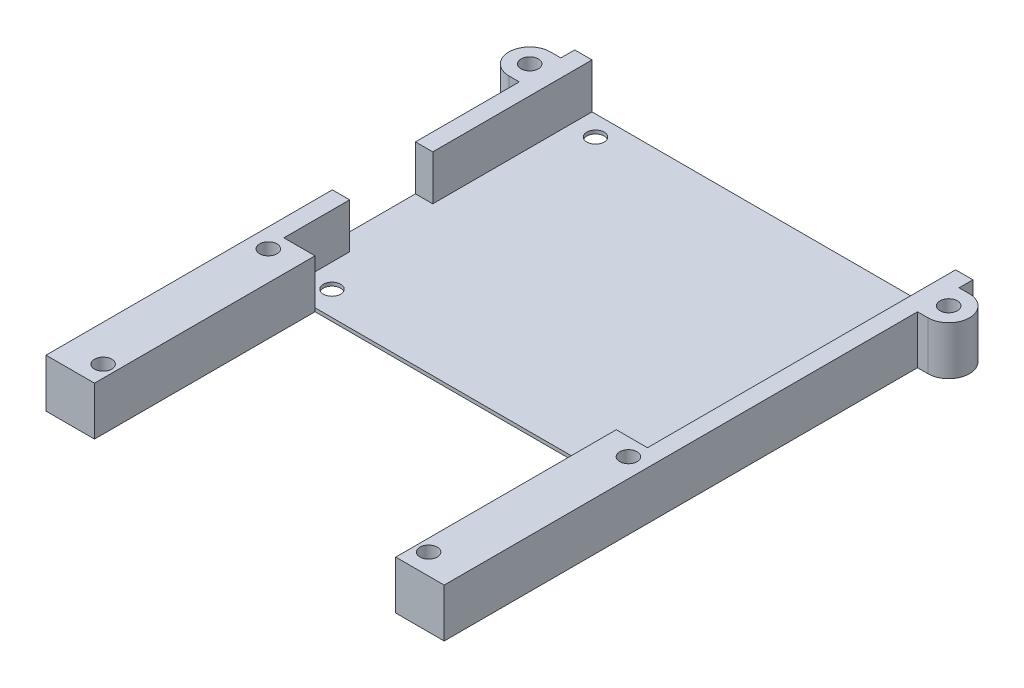
SolidWorks part; units mm, degrees
ref_plane "Front Plane" through (0, 0, 0) normal (0, 0, 1) x (1, 0, 0)
ref_plane "Top Plane" through (0, 0, 0) normal (0, 1, 0) x (1, 0, 0)
ref_plane "Right Plane" through (0, 0, 0) normal (1, 0, 0) x (0, 0, -1)
sketch "Sketch1" plane through (0, 0, 0) normal (0, 1, 0) x (1, 0, 0)
  line L0 (0, 0) -> (0, 76.35) construction
  line L1 (-28.75, 76.35) -> (28.75, 76.35)
  line L2 (28.75, 76.35) -> (28.75, 0)
  line L3 (28.75, 0) -> (21.75, 0)
  line L4 (21.75, 0) -> (21.75, 31.85)
  line L5 (21.75, 31.85) -> (-21.75, 31.85)
  line L6 (-21.75, 31.85) -> (-21.75, 0)
  line L7 (-21.75, 0) -> (-28.75, 0)
  line L8 (-28.75, 0) -> (-28.75, 76.35)
  line L9 (-26.25, 76.35) -> (-26.25, 31.85)
  line L14 (-26.25, 31.85) -> (-21.75, 31.85)
  line L15 (26.25, 76.35) -> (26.25, 31.85)
  line L16 (26.25, 31.85) -> (21.75, 31.85)
  line L17 (28.75, 74.35) -> (30.25, 74.35)
  line L18 (-28.75, 41.35) -> (-26.25, 41.35)
  line L19 (-28.75, 41.35) -> (-28.75, 53.35)
  line L20 (-28.75, 53.35) -> (-26.25, 53.35)
  line L21 (-26.25, 41.35) -> (-26.25, 53.35)
  line L22 (30.25, 68.35) -> (28.75, 68.35)
  line L23 (-30.25, 68.35) -> (-28.75, 68.35)
  line L24 (-28.75, 74.35) -> (-30.25, 74.35)
  arc A0 (30.25, 68.35) -> (30.25, 74.35) centre (30.25, 71.35) ccw
  arc A1 (-30.25, 68.35) -> (-30.25, 74.35) centre (-30.25, 71.35) cw
  point P10 (0, 76.35)
  point P16 (-27.5, 41.35)
  point P17 (-22.85, 73.45)
  point P18 (22.85, 73.45)
  point P23 (22.85, 35.4)
  point P24 (-22.85, 35.4)
  point P25 (23.5, 3)
  point P26 (26, 29.35)
  point P27 (-26, 29.35)
  point P28 (-23.5, 3)
  point P40 (30.25, 71.35)
  point P41 (-30.25, 71.35)
  dimension "D16" = 3
  dimension "D1" = 2.5
  dimension "D2" = 7
  dimension "D3" = 43.5
  dimension "D4" = 31.85
  dimension "D5" = 44.5
  dimension "D6" = 23
  dimension "D7" = 12
  dimension "D8" = 22.85
  dimension "D9" = 38.05
  dimension "D10" = 2.9
  dimension "D11" = 47
  dimension "D12" = 52
  dimension "D13" = 47
  dimension "D14" = 3
  dimension "D15" = 1.5
  dimension "D17" = 2
extrude "Boss-Extrude1" add sketch "Sketch1" along normal blind 0.5 contours L5 L0 L1 L9 L14 | L0 L5 L16 L15 L1 | L20 L8 L18 L9 region at (-13.125, 0, -54.1) region at (13.125, 0, -54.1) region at (-27.5, 0, -47.35)
extrude "Boss-Extrude2" add sketch "Sketch1<3>" along normal blind 7 contours L18 L8 L7 L6 L14 L9 | L8 L20 L9 L1 | L15 L16 L4 L3 L2 L1 | A1 L23 L8 L24 | L22 A0 L17 L2 region at (-27.5, 0, -64.85) region at (-30.7362, 0, -71.35) region at (25.999, 0, -28.6329) region at (-25.4666, 0, -17.9154) region at (30.7362, 0, -71.35)
sketch "Sketch1<3>" plane through (0, 0, 0) normal (0, 1, 0) x (1, 0, 0) same geometry as "Sketch1"
hole_wizard "Ø2.5 (2.5) Diameter Hole1" positions "Sketch4" profile "Sketch5" hole size "Ø2.5" standard "ANSI Metric"
sketch "Sketch4" plane through (0, 0, 0) normal (0, -1, 0) x (-1, 0, 0)
  point P0 (-22.85, 73.45)
  point P3 (22.85, 73.45)
  point P6 (26, 29.35)
  point P9 (22.85, 35.4)
  point P12 (-22.85, 35.4)
  point P15 (-26, 29.35)
  point P18 (-23.5, 3)
  point P21 (23.5, 3)
  point P24 (-30.25, 71.35)
  point P27 (30.25, 71.35)
sketch "Sketch5" plane through (22.85, 0, -73.45) normal (1, 0, 0) x (0, 0, -1)
  line L0 (0, 0) -> (0, 12.7511)
  line L1 (0, 12.7511) -> (1.25, 12)
  line L2 (1.25, 12) -> (1.25, 0)
  line L5 (1.25, 0) -> (0, 0)
  line L10 (0, 12.7511) -> (-1.25, 12) construction
  line L11 (0, -6.35) -> (0, 107.95) construction
  dimension "Hole Dia." = 2.5
  dimension "Hole Depth" = 12
  dimension "Drill Angle" = 118
